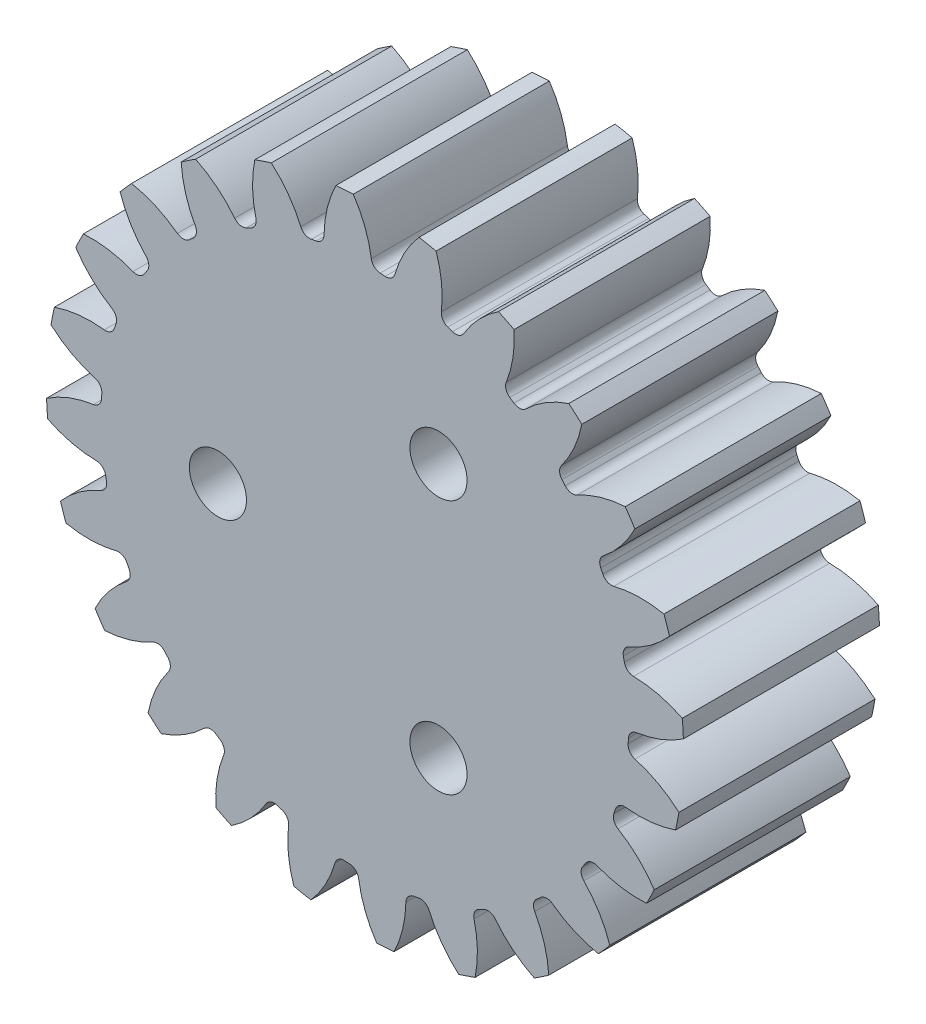
SolidWorks part; units mm, degrees
ref_plane "Front" through (0, 0, 0) normal (0, 0, 1) x (1, 0, 0)
ref_plane "Top" through (0, 0, 0) normal (0, 1, 0) x (1, 0, 0)
ref_plane "Right" through (0, 0, 0) normal (1, 0, 0) x (0, 0, -1)
sketch "Sketch3" plane through (0, 0, 0) normal (0, 0, 1) x (1, 0, 0)
  circle A0 centre (0, 0) radius 20.6375
  dimension "od" = 41.275
extrude "gearBody" add sketch "Sketch3" along normal blind 12.7
sketch "Sketch2" plane through (0, 0, 0) normal (0, 0, 1) x (1, 0, 0)
  line L0 (0, 0) -> (16.5385, 6.8505) construction
  line L1 (22.0347, -5.709) -> (0, 0) construction
  line L2 (0, 0) -> (36.3143, 0) construction
  line L3 (19.05, -0.043) -> (18.8852, -2.5004) construction
  line L5 (18.9676, -1.2717) -> (0, 0) construction
  line L7 (0, 0) -> (17.9011, 0) construction
  arc A0 (17.8975, -0.3593) -> (17.7853, -2.0332) centre (0, 0) ccw construction
  arc A1 (20.6236, 0.7563) -> (20.3381, -3.5027) centre (0, 0) ccw construction
  arc A2 (19.05, -0.043) -> (18.8852, -2.5004) centre (0, 0) ccw construction
  arc A3 (17.0444, -1.304) -> (17.0659, -0.983) centre (0, 0) ccw
  arc A4 (22.0347, -5.709) -> (17.4884, -1.9416) centre (15.476, -8.9969) ccw
  arc A5 (22.0347, -5.709) -> (22.5996, 2.7164) centre (0, 0) ccw
  arc A6 (22.5996, 2.7164) -> (17.5911, -0.4103) centre (16.5385, 6.8505) cw
  arc A7 (17.0659, -0.983) -> (17.5911, -0.4103) centre (17.6793, -1.0183) cw
  arc A8 (17.4884, -1.9416) -> (17.0444, -1.304) centre (17.657, -1.3509) cw
  point P6 (22.5996, 2.7164)
  point P22 (22.0347, -5.709)
  dimension "baseDia" = 35.8023
  dimension "od" = 41.275
  dimension "pd" = 38.1
  dimension "rd" = 34.1884
  dimension "rFillet" = 0.6144
  dimension "pointX" = 22.5996
  dimension "pointY" = 2.7164
  dimension "CTT" = 2.4574
  dimension "flankCenterAngle" = 22.5
extrude "toothCut" cut sketch "Sketch2" along normal through all
pattern_circular "CirPattern1" count 24 over 360 about axis through (0, 0, 12.7) along (0, 0, -1) of "toothCut"
sketch "hub1Dia" plane through (0, 0, 0) normal (0, 0, -1) x (-1, 0, 0)
  circle A0 centre (0, 0) radius 12.7
  dimension "hub1Dia" = 25.4
sketch "hub2Dia" plane through (0, 0, 12.7) normal (0, 0, 1) x (1, 0, 0)
  circle A0 centre (0, 0) radius 12.7
  dimension "hub2dia" = 25.4
sketch "boreDia" plane through (0, 0, 0) normal (0, 0, 1) x (1, 0, 0)
  circle A0 centre (0, 0) radius 6.35
  dimension "boreDia" = 12.7
sketch "Sketch4" plane through (0, 0, 0) normal (0, 0, -1) x (-1, 0, 0)
  circle A0 centre (9.525, 0) radius 1.85
  circle A1 centre (-4.7625, -8.2489) radius 1.85
  circle A2 centre (-4.7625, 8.2489) radius 1.85
  point P9 (0, 0)
  dimension "D2" = 3.7
  dimension "D1" = 9.525
  dimension "D3" = 3
extrude "Cut-Extrude1" cut sketch "Sketch4" against normal through all
equation "\"D2@Sketch4\"=3.7mm"
